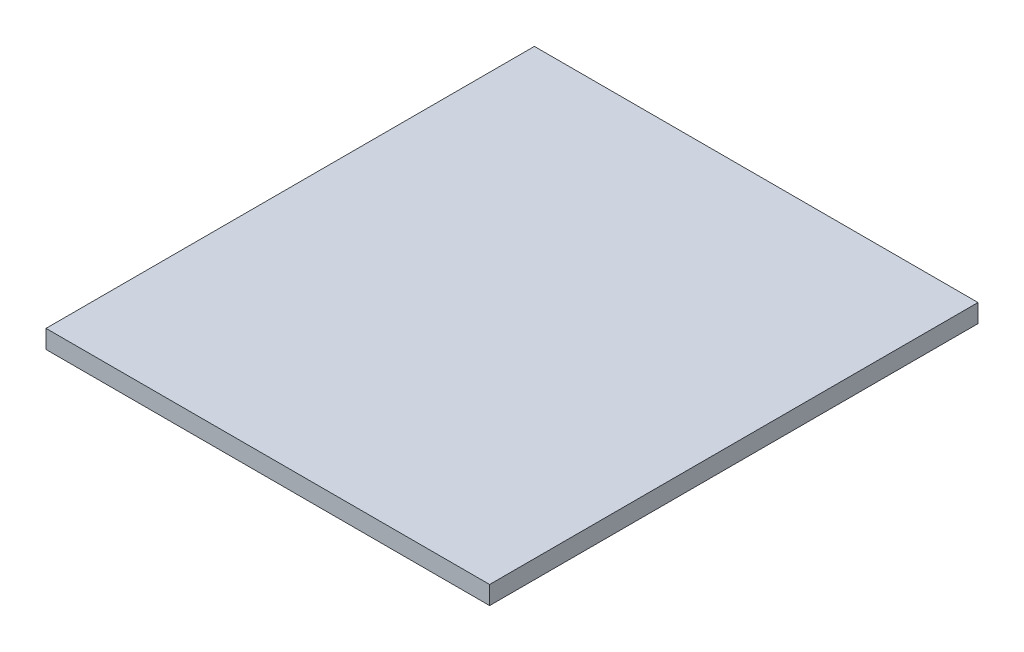
SolidWorks part; units mm, degrees
material "Perspex (TM) GS Acrylic Cast Sheet"
ref_plane "Front Plane" through (0, 0, 0) normal (0, 0, 1) x (1, 0, 0)
ref_plane "Top Plane" through (0, 0, 0) normal (0, 1, 0) x (1, 0, 0)
ref_plane "Right Plane" through (0, 0, 0) normal (1, 0, 0) x (0, 0, -1)
sketch "Sketch1" plane through (0, 0, 0) normal (0, 1, 0) x (1, 0, 0)
  line L1 (-109, -120) -> (109, -120)
  line L2 (-109, -120) -> (-109, 120)
  line L3 (-109, 120) -> (109, 120)
  line L4 (109, -120) -> (109, 120)
  line L5 (-109, -120) -> (109, 120) construction
  line L6 (-109, 120) -> (109, -120) construction
  point P0 (0, 0)
  dimension "D2" = 240
  dimension "D1" = 218
extrude "Boss-Extrude1" add sketch "Sketch1" along normal blind 9
equation "\"PCLength\"= 145mm'Length across I/O from PS to GPU"
equation "\"PCWidth\"= 340mm'Distance of longest part parallel to GPU(ussually GPU)"
equation "\"PCHeight\"= 180mm'Tallest point with mobo laying flat"
equation "\"WallThickness\"= 9mm'Thickness of each outer tank wall"
equation "\"ThermoBarrierThickness\"= 6mm'Thickness of barrier between hot side and cold side"
equation "\"HotSideGap\"= 36mm'Space in the hot side for a pump"
equation "\"PCClearance\"= 40mm'Clearance from top of tank to top of PC"
equation "\"RadiatorHeight\"= 275mm'Final Height from ground of radiators"
equation "\"D2@Sketch1\"=\"PCHeight\" + \"ThermoBarrierThickness\" + \"HotSideGap\" + (2 * \"WallThickness\")"
equation "\"D1@Boss-Extrude1\"=\"WallThickness\""
equation "\"D1@Sketch1\"=\"PCLength\" + (2 * \"WallThickness\") + \"AirflowGap\" + 30"
equation "\"AirflowGap\"= 25mm'Distance between radiators and tank for airflow"
equation "\"VolumeSubtraction\"= 230mm"
